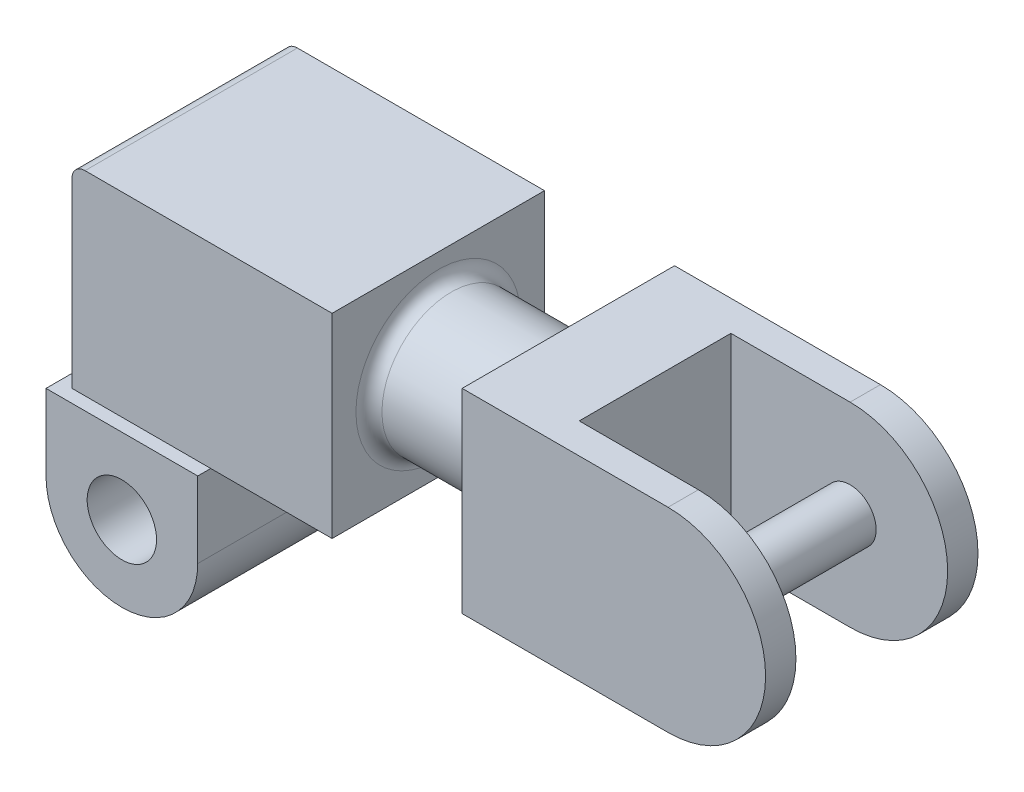
SolidWorks part; units mm, degrees
material "Aleación 1060"
ref_plane "Ön Düzlem" through (0, 0, 0) normal (0, 0, 1) x (1, 0, 0)
ref_plane "Üst Düzlem" through (0, 0, 0) normal (0, 1, 0) x (1, 0, 0)
ref_plane "Sağ Düzlem" through (0, 0, 0) normal (1, 0, 0) x (0, 0, -1)
sketch "Çizim1" plane through (0, 0, 0) normal (0, 0, 1) x (1, 0, 0)
  line L0 (-17.5, 0) -> (-17.5, 17.5)
  line L1 (-17.5, 17.5) -> (17.5, 17.5)
  line L2 (17.5, 17.5) -> (17.5, 0)
  arc A0 (-17.5, 0) -> (17.5, 0) centre (0, 0) ccw
  circle A1 centre (0, 0) radius 8
  dimension "D1" = 17.5
  dimension "D2" = 16
extrude "Yükseklik-Ekstrüzyon1" add sketch "Çizim1" along normal mid plane 55
sketch "Çizim3" plane through (0, 17.5, 0) normal (0, 1, 0) x (1, 0, 0)
  line L0 (17.5, 27.5) -> (-17.5, 27.5) construction
  line L1 (45.5, -24.5) -> (-14.5, -24.5)
  line L2 (45.5, -24.5) -> (45.5, 24.5)
  line L3 (45.5, 24.5) -> (-14.5, 24.5)
  line L4 (-14.5, -24.5) -> (-14.5, 24.5)
  line L5 (45.5, -24.5) -> (-14.5, 24.5) construction
  line L6 (45.5, 24.5) -> (-14.5, -24.5) construction
  line L7 (-17.5, -27.5) -> (-17.5, 27.5) construction
  point P0 (15.5, 0)
  dimension "D1" = 3
  dimension "D2" = 3
  dimension "D3" = 60
extrude "Yükseklik-Ekstrüzyon2" add sketch "Çizim3" along normal blind 45
sketch "Çizim4" plane through (45.5, 0, 0) normal (1, 0, 0) x (0, 0, -1)
  line L0 (24.5, 62.5) -> (24.5, 17.5) construction
  circle A0 centre (0, 40) radius 16
  point P6 (24.5, 40)
  dimension "D1" = 32
extrude "Yükseklik-Ekstrüzyon3" add sketch "Çizim4" along normal blind 30
sketch "Çizim7" plane through (0, 62.5, 0) normal (0, 1, 0) x (1, 0, 0)
  line L0 (75.5, -24.5) -> (75.5, 24.5)
  line L1 (75.5, -16) -> (75.5, 16) construction
  line L2 (75.5, 24.5) -> (145.5, 24.5)
  line L3 (145.5, 24.5) -> (145.5, 17.5)
  line L4 (145.5, 17.5) -> (95.5, 17.5)
  line L5 (95.5, 17.5) -> (95.5, -17.5)
  line L6 (95.5, -17.5) -> (145.5, -17.5)
  line L7 (145.5, -17.5) -> (145.5, -24.5)
  line L8 (145.5, -24.5) -> (75.5, -24.5)
  line L9 (45.5, 24.5) -> (-14.5, 24.5) construction
  line L10 (-14.5, -24.5) -> (45.5, -24.5) construction
  dimension "D1" = 7
  dimension "D2" = 20
  dimension "D3" = 50
extrude "Yükseklik-Ekstrüzyon4" add sketch "Çizim7" against normal blind 45
fillet "Radyus1" 2 edges at (145.5, 62.5, 21) (145.5, 17.5, 21) type full round first side face at (115.5, 62.5, 0) second side face at (115.5, 17.5, 0) middle face at (145.5, 40, 21)
fillet "Radyus2" 2 edges at (145.5, 62.5, -21) (145.5, 17.5, -21) type full round first side face at (109.875, 62.5, 0) second side face at (109.875, 17.5, 0) middle face at (145.5, 40, -21)
fillet "Radyus3" radius 3 3 edges at (-14.5, 62.5, 0) (75.5, 40, -16) (45.5, 40, -16)
sketch "Çizim8" plane through (0, 0, -17.5) normal (0, 0, 1) x (1, 0, 0)
  circle A0 centre (123, 40) radius 6
  dimension "D1" = 12
extrude "Yükseklik-Ekstrüzyon5" add sketch "Çizim8" along normal blind 35
